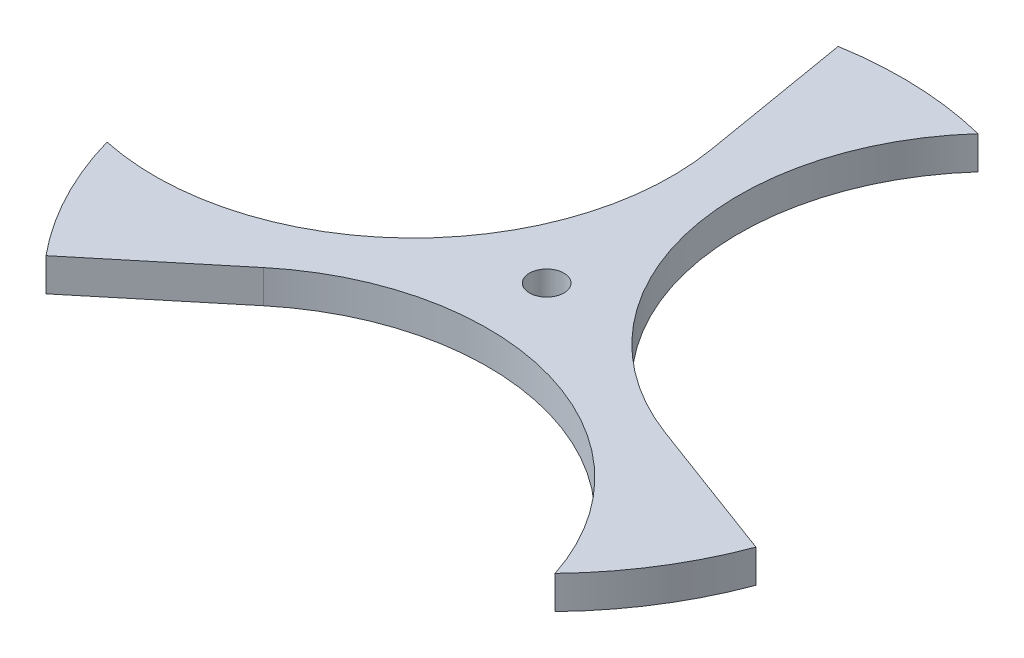
SolidWorks part; units mm, degrees
ref_plane "Front" through (0, 0, 0) normal (0, 0, 1) x (1, 0, 0)
ref_plane "Top" through (0, 0, 0) normal (0, 1, 0) x (1, 0, 0)
ref_plane "Right" through (0, 0, 0) normal (1, 0, 0) x (0, 0, -1)
ref_axis "side-side" through (80.9, 0, 0) along (-1, 0, 0)
ref_axis "up-down" through (0, 50, 0) along (0, -1, 0)
ref_axis "front-back" through (0, 0, -80.9) along (0, 0, 1)
sketch "Sketch3" plane through (0, 0, 0) normal (0, 1, 0) x (1, 0, 0)
  circle A0 centre (0, 0) radius 65.5152 construction
  circle A1 centre (0, 0) radius 65.5152 construction
  circle A2 centre (0, 0) radius 12.7 construction
  circle A3 centre (0, 0) radius 12.7 construction
sketch "Sketch1" plane through (0, 0, 0) normal (0, 1, 0) x (1, 0, 0)
  line L0 (34.7005, -12.9165) -> (61.3996, -22.8547)
  line L1 (0, 0) -> (51.3143, 31.7167) construction
  line L2 (0, 0) -> (1.8103, -60.2978) construction
  line L3 (0, 0) -> (-53.1246, 28.5812) construction
  line L4 (-28.5363, -23.5933) -> (-50.4925, -41.7462)
  line L5 (-6.1642, 36.5098) -> (-10.9071, 64.6009)
  circle A0 centre (0, 0) radius 65.5152 construction
  arc A1 (15.8978, 63.5571) -> (-10.9071, 64.6009) centre (0, 0) ccw
  circle A2 centre (51.3143, 31.7167) radius 47.625 construction
  arc A3 (15.8978, 63.5571) -> (34.7005, -12.9165) centre (51.3143, 31.7167) ccw
  circle A4 centre (0, 0) radius 12.7 construction
  circle A5 centre (0, 0) radius 12.7 construction
  arc A6 (47.0931, -45.5464) -> (-28.5363, -23.5933) centre (1.8103, -60.2978) ccw
  arc A7 (-62.9909, -18.0107) -> (-6.1642, 36.5098) centre (-53.1246, 28.5812) ccw
  arc A8 (47.0931, -45.5464) -> (61.3996, -22.8547) centre (0, 0) ccw
  arc A9 (-62.9909, -18.0107) -> (-50.4925, -41.7462) centre (0, 0) ccw
  circle A10 centre (0, 0) radius 3.175
  dimension "D3" = 6.35
  dimension "D1" = 120
  dimension "D2" = 120
extrude "Boss-Extrude1" add sketch "Sketch1" along normal mid plane 6.096
sketch "Sketch2" plane through (0, 0, 0) normal (0, 0, 1) x (1, 0, 0)
  line L0 (51.3143, -50) -> (51.3143, 50) construction
  arc A0 (0, 0) -> (51.3143, 51.3143) centre (51.3143, 0) cw
